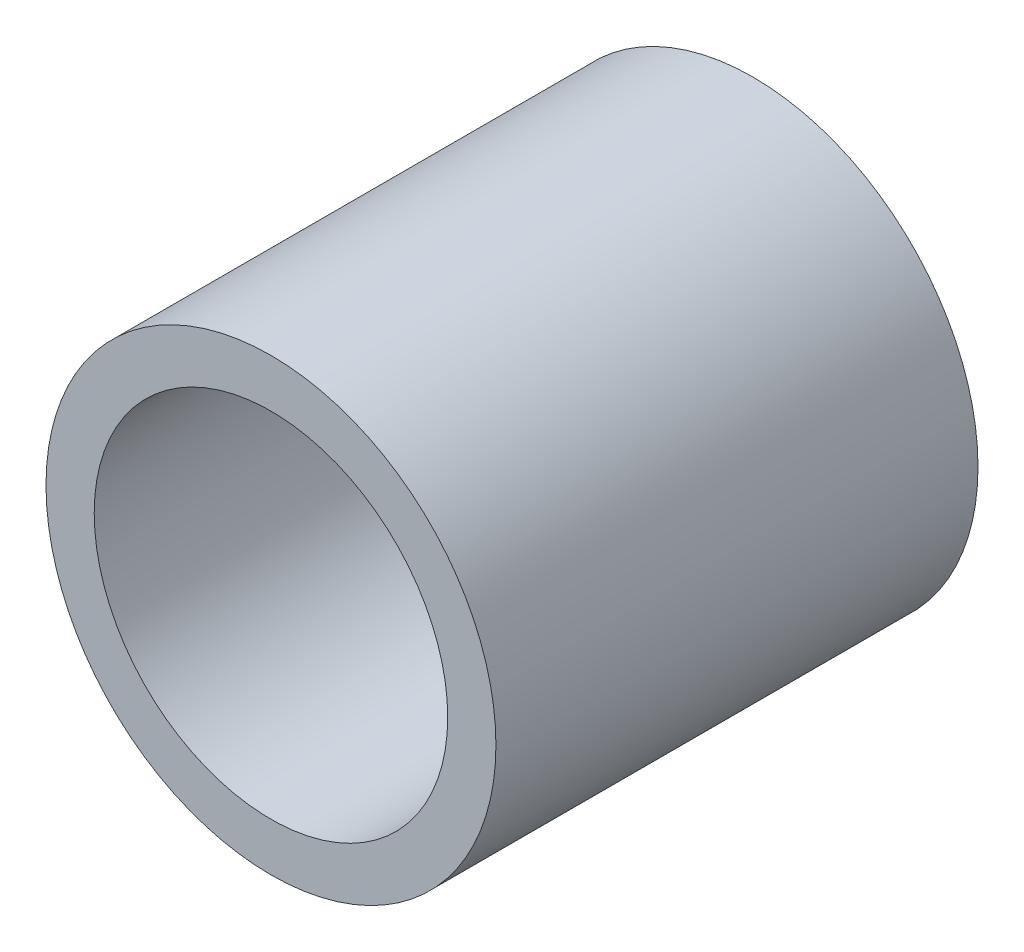
SolidWorks part; units mm, degrees
ref_plane "Front Plane" through (0, 0, 0) normal (0, 0, 1) x (1, 0, 0)
ref_plane "Top Plane" through (0, 0, 0) normal (0, 1, 0) x (1, 0, 0)
ref_plane "Right Plane" through (0, 0, 0) normal (1, 0, 0) x (0, 0, -1)
sketch "Sketch3" plane through (0, 0, 0) normal (0, 0, 1) x (1, 0, 0)
  line L0 (-120.13, 3.5549) -> (124.87, 3.5549) construction
  line L1 (-120.13, 63.5549) -> (124.87, 63.5549)
  line L2 (-120.13, 63.5549) -> (-120.13, -56.4451)
  line L3 (-120.13, -56.4451) -> (124.87, -56.4451)
  line L4 (124.87, 63.5549) -> (124.87, -56.4451)
  line L5 (2.37, 63.5549) -> (2.37, -56.4451) construction
  line L14 (-4.9072, 3.5549) -> (2.37, -3.7222)
  line L18 (2.37, 29.5357) -> (24.87, -9.4354)
  line L20 (-20.13, -9.4354) -> (13.62, 10.0501) construction
  line L21 (24.87, -9.4354) -> (-8.88, 10.0501) construction
  line L22 (2.37, 29.5357) -> (2.37, 0) construction
  circle A0 centre (74.87, 3.5549) radius 22.5
  circle A1 centre (74.87, 3.5549) radius 35
  circle A2 centre (74.87, 3.5549) radius 27.5
  point P4 (-67.63, 3.5549)
  point P10 (-67.63, 3.5549)
  point P20 (2.37, 3.5549)
  point P27 (7.7505, -5.3087)
  point P28 (2.37, 3.5549)
  point P32 (-67.63, 3.5549)
  point P38 (-67.63, 3.5549)
  dimension "D2" = 50
  dimension "D3" = 70
  dimension "cylinder" = 45
  dimension "D6" = 55
  dimension "triangle3" = 45
  dimension "triangle2" = 45
  dimension "triangle" = 45
extrude "Boss-Extrude4" add sketch "Sketch3" against normal blind 75 contours A1 A2 region at (40.8599, 3.5549, 0)
